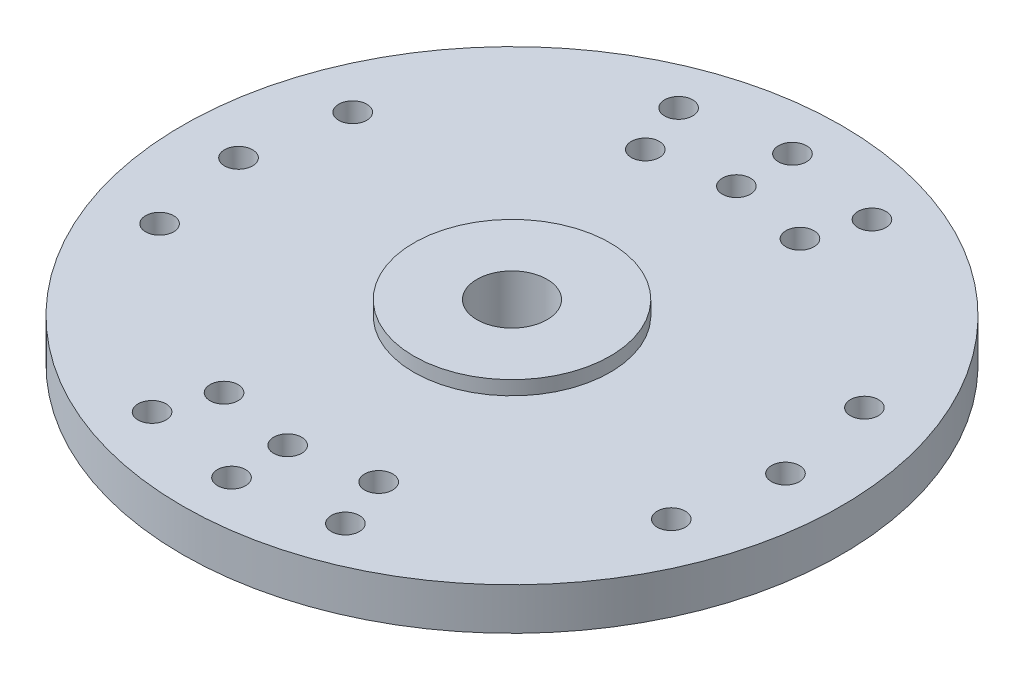
SolidWorks part; units mm, degrees
ref_plane "Front Plane" through (0, 0, 0) normal (0, 0, 1) x (1, 0, 0)
ref_plane "Top Plane" through (0, 0, 0) normal (0, 1, 0) x (1, 0, 0)
ref_plane "Right Plane" through (0, 0, 0) normal (1, 0, 0) x (0, 0, -1)
ref_axis "Axis1" through (0, 2.215, 0) along (0, -1, 0)
sketch "Sketch1" plane through (0, 0, 0) normal (0, 1, 0) x (1, 0, 0)
  line L1 (0, 0) -> (11.75, 0) construction
  line L3 (0, 3.5) -> (0, -3.5) construction
  circle A0 centre (0, 0) radius 3.5 construction
  circle A2 centre (0, 0) radius 11.75
  dimension "D1" = 23.5
  dimension "D2" = 7
extrude "Boss-Extrude1" add sketch "Sketch1" along normal blind 1.5
sketch "Sketch2" plane through (0, 1.5, 0) normal (0, 1, 0) x (1, 0, 0)
  circle A0 centre (0, 0) radius 3.5
  dimension "D1" = 7
extrude "Boss-Extrude2" add sketch "Sketch2" against normal blind 4.3 from offset 0.5
sketch "Sketch3" plane through (0, 2, 0) normal (0, 1, 0) x (1, 0, 0)
  circle A8 centre (0, 0) radius 1.25
  dimension "D3" = 2.5
extrude "Cut-Extrude1" cut sketch "Sketch3" against normal through all both and the other way through all
sketch "Sketch4" plane through (0, 1.5, 0) normal (0, 1, 0) x (1, 0, 0)
  line L0 (0, 0) -> (9.75, 0) construction
  circle A0 centre (9.75, 0) radius 0.5
  circle A1 centre (0, 0) radius 9.75 construction
  circle A2 centre (9.1218, 3.4432) radius 0.5
  circle A3 centre (9.1218, -3.4432) radius 0.5
  point P9 (0, 0)
  dimension "D2" = 1
  dimension "D1" = 9.75
  dimension "D3" = 3.5
extrude "Cut-Extrude2" cut sketch "Sketch4" against normal through all
sketch "Sketch5" plane through (0, 0, 0) normal (0, 1, 0) x (1, 0, 0)
  line L0 (-3.446, 9.3875) -> (0, 0) construction
  line L1 (0, 0) -> (0, 10) construction
  circle A0 centre (0, 8) radius 0.5
  circle A1 centre (0, 10) radius 0.5
  circle A2 centre (3.446, 9.3875) radius 0.5
  circle A3 centre (2.7568, 7.51) radius 0.5
  circle A4 centre (-2.7568, 7.51) radius 0.5
  circle A5 centre (-3.446, 9.3875) radius 0.5
  circle A6 centre (0, 0) radius 8 construction
  circle A7 centre (0, 0) radius 10 construction
  circle A8 centre (9.75, 0) radius 0.5 construction
  point P16 (-2.0293, 7.7552)
  point P17 (-2.0967, 7.7734)
  point P18 (-2.8227, 9.4879)
  dimension "D1" = 20
  dimension "D3" = 16
  dimension "D2" = 3.5
extrude "Cut-Extrude3" cut sketch "Sketch5" against normal through all both and the other way through all
pattern_circular "CirPattern1" count 2 over 360 about axis through (0, 2.215, 0) along (0, -1, 0) of "Cut-Extrude2", "Cut-Extrude3"
sketch "Sketch6" plane through (0, -2.3, 0) normal (0, -1, 0) x (1, 0, 0)
  circle A0 centre (0, 0) radius 2.375
  dimension "D1" = 4.75
extrude "Cut-Extrude4" cut sketch "Sketch6" against normal blind 2.25
